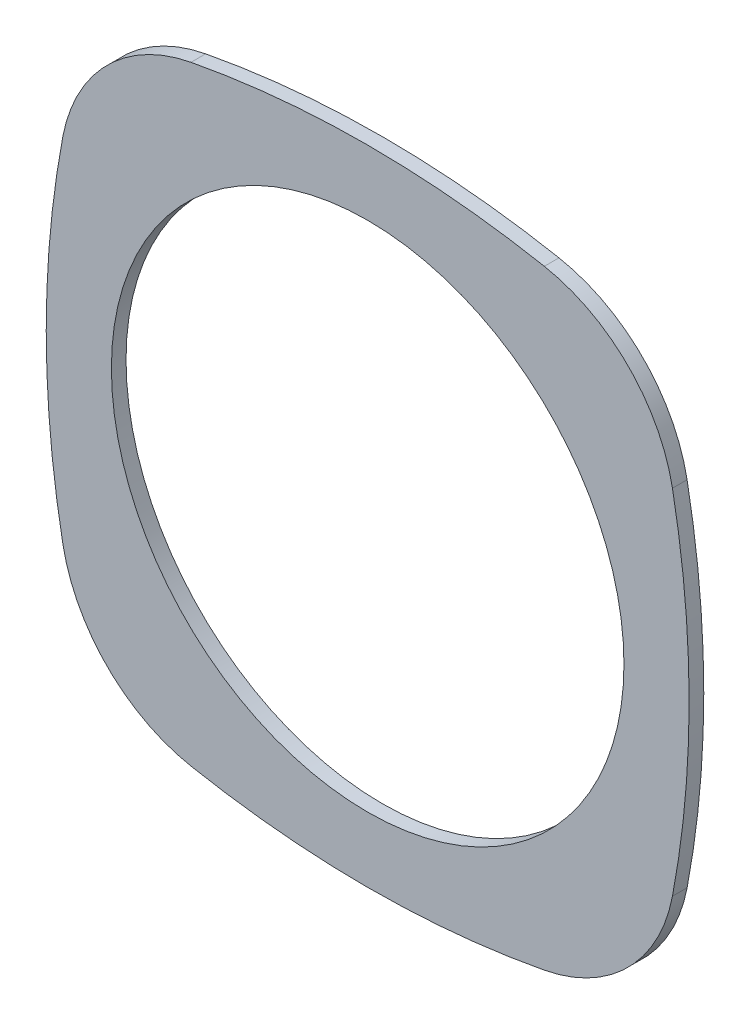
SolidWorks part; units mm, degrees
ref_plane "Front" through (0, 0, 0) normal (0, 0, 1) x (1, 0, 0)
ref_plane "Top" through (0, 0, 0) normal (0, 1, 0) x (1, 0, 0)
ref_plane "Side" through (0, 0, 0) normal (1, 0, 0) x (0, 0, -1)
ref_axis "X_Axis" through (-20.1896, 0, 0) along (1, 0, 0)
ref_axis "Y_Axis" through (0, -14.8261, 0) along (0, 1, 0)
ref_axis "Z_Axis" through (0, 0, -19.842) along (0, 0, 1)
sketch "Sketch1" plane through (0, 0, 0) normal (0, 0, 1) x (1, 0, 0)
  circle A0 centre (0, 0) radius 17.5
  arc A8 (12.0638, 20.8113) -> (-12.0638, 20.8113) centre (0, -42.5226) ccw
  arc A9 (-12.0638, 20.8113) -> (-20.8113, 12.0638) centre (-10.0056, 10.0056) ccw
  arc A10 (-20.8113, 12.0638) -> (-20.8113, -12.0638) centre (42.5226, 0) ccw
  arc A11 (-20.8113, -12.0638) -> (-12.0638, -20.8113) centre (-10.0056, -10.0056) ccw
  arc A12 (-12.0638, -20.8113) -> (12.0638, -20.8113) centre (0, 42.5226) ccw
  arc A13 (12.0638, -20.8113) -> (20.8113, -12.0638) centre (10.0056, -10.0056) ccw
  arc A14 (20.8113, -12.0638) -> (20.8113, 12.0638) centre (-42.5226, 0) ccw
  arc A15 (20.8113, 12.0638) -> (12.0638, 20.8113) centre (10.0056, 10.0056) ccw
  arc A16 (12.0638, 20.8113) -> (-12.0638, 20.8113) centre (0, -42.5226) ccw
  arc A17 (-12.0638, 20.8113) -> (-20.8113, 12.0638) centre (-10.0056, 10.0056) ccw
  arc A18 (-20.8113, 12.0638) -> (-20.8113, -12.0638) centre (42.5226, 0) ccw
  arc A19 (-20.8113, -12.0638) -> (-12.0638, -20.8113) centre (-10.0056, -10.0056) ccw
  arc A20 (-12.0638, -20.8113) -> (12.0638, -20.8113) centre (0, 42.5226) ccw
  arc A21 (12.0638, -20.8113) -> (20.8113, -12.0638) centre (10.0056, -10.0056) ccw
  arc A22 (20.8113, -12.0638) -> (20.8113, 12.0638) centre (-42.5226, 0) ccw
  arc A23 (20.8113, 12.0638) -> (12.0638, 20.8113) centre (10.0056, 10.0056) ccw
  dimension "D1" = 0
extrude "Boss-Extrude1" add sketch "Sketch1" along normal blind 1
